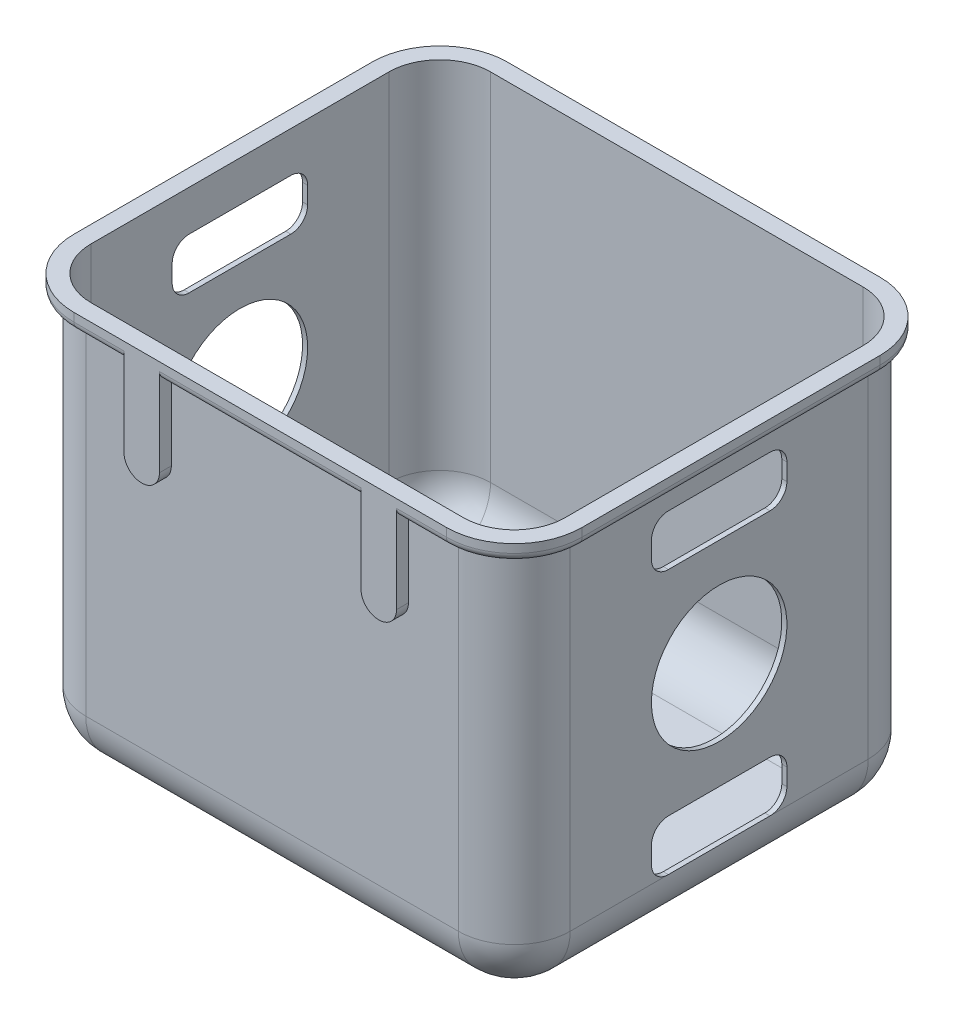
SolidWorks part; units mm, degrees
ref_plane "Front Plane" through (0, 0, 0) normal (0, 0, 1) x (1, 0, 0)
ref_plane "Top Plane" through (0, 0, 0) normal (0, 1, 0) x (1, 0, 0)
ref_plane "Right Plane" through (0, 0, 0) normal (1, 0, 0) x (0, 0, -1)
sketch "Sketch1" plane through (0, 0, 0) normal (0, 1, 0) x (1, 0, 0)
  line L1 (-145.5235, 110.6147) -> (140.4765, 110.6147)
  line L2 (-145.5235, 110.6147) -> (-145.5235, -131.3853)
  line L3 (-145.5235, -131.3853) -> (140.4765, -131.3853)
  line L4 (140.4765, 110.6147) -> (140.4765, -131.3853)
  dimension "D1" = 286
  dimension "D2" = 242
extrude "Boss-Extrude1" add sketch "Sketch1" along normal blind 243
fillet "Fillet1" radius 33 8 edges at (-2.5235, 0, 131.3853) (140.4765, 0, 10.3853) (-2.5235, 0, -110.6147) (-145.5235, 0, 10.3853) (-145.5235, 121.5, -110.6147) (-145.5235, 121.5, 131.3853) (140.4765, 121.5, -110.6147) (140.4765, 121.5, 131.3853)
shell "Shell1" thickness 3 removed face at (-2.5235, 243, 10.3853)
sketch "Sketch3" plane through (-145.5235, 0, 0) normal (-1, 0, 0) x (0, 0, 1)
  line L0 (-29.6147, 204) -> (50.3853, 204) construction
  line L5 (98.3853, 0) -> (-77.6147, 0) construction
  line L6 (-77.6147, 33) -> (98.3853, 33) construction
  line L7 (40.3853, 219) -> (-19.6147, 219)
  line L8 (50.3853, 209) -> (50.3853, 199)
  line L9 (40.3853, 189) -> (-19.6147, 189)
  line L10 (-29.6147, 209) -> (-29.6147, 199)
  line L11 (-110.6147, 33) -> (-110.6147, 243) construction
  line L12 (-19.6147, 63) -> (40.3853, 63)
  line L13 (-29.6147, 53) -> (-29.6147, 43)
  line L14 (-19.6147, 33) -> (40.3853, 33)
  line L15 (50.3853, 53) -> (50.3853, 43)
  arc A0 (40.3853, 33) -> (50.3853, 43) centre (40.3853, 43) ccw
  arc A1 (-29.6147, 43) -> (-19.6147, 33) centre (-19.6147, 43) ccw
  arc A2 (40.3853, 63) -> (50.3853, 53) centre (40.3853, 53) cw
  arc A3 (-19.6147, 63) -> (-29.6147, 53) centre (-19.6147, 53) ccw
  arc A4 (40.3853, 219) -> (50.3853, 209) centre (40.3853, 209) cw
  arc A5 (50.3853, 199) -> (40.3853, 189) centre (40.3853, 199) cw
  arc A6 (-19.6147, 189) -> (-29.6147, 199) centre (-19.6147, 199) cw
  arc A7 (-29.6147, 209) -> (-19.6147, 219) centre (-19.6147, 209) cw
  circle A12 centre (10.3853, 126) radius 40
  point P4 (10.3853, 204)
  point P28 (50.3853, 219)
  point P31 (50.3853, 189)
  point P38 (50.3853, 166)
  point P41 (50.3853, 86)
  point P46 (-29.6147, 166)
  dimension "D7" = 10
  dimension "D9" = 80
  dimension "D2" = 80
  dimension "D3" = 80
  dimension "D4" = 121
  dimension "D5" = 30
  dimension "D6" = 63
  dimension "D10" = 126
extrude "Cut-Extrude1" cut sketch "Sketch3" against normal through all
sketch "Sketch6" plane through (0, 243, 0) normal (0, 1, 0) x (1, 0, 0)
  line L0 (140.4765, -98.3853) -> (140.4765, 77.6147) construction
  line L1 (-112.5235, 117.6147) -> (107.4765, 117.6147)
  line L2 (-152.5235, 77.6147) -> (-152.5235, -98.3853)
  line L3 (-112.5235, -138.3853) -> (107.4765, -138.3853)
  line L4 (147.4765, 77.6147) -> (147.4765, -98.3853)
  line L5 (-112.5235, 110.6147) -> (107.4765, 110.6147)
  line L6 (-145.5235, 77.6147) -> (-145.5235, -98.3853)
  line L7 (-112.5235, -131.3853) -> (107.4765, -131.3853)
  line L8 (140.4765, 77.6147) -> (140.4765, -98.3853)
  line L9 (107.4765, 110.6147) -> (-112.5235, 110.6147) construction
  line L10 (-145.5235, 77.6147) -> (-145.5235, -98.3853) construction
  line L12 (-112.5235, -131.3853) -> (107.4765, -131.3853) construction
  arc A0 (-112.5235, -131.3853) -> (-145.5235, -98.3853) centre (-112.5235, -98.3853) cw
  arc A1 (107.4765, 110.6147) -> (140.4765, 77.6147) centre (107.4765, 77.6147) cw
  arc A2 (-145.5235, 77.6147) -> (-112.5235, 110.6147) centre (-112.5235, 77.6147) cw
  arc A3 (107.4765, -131.3853) -> (140.4765, -98.3853) centre (107.4765, -98.3853) ccw
  arc A4 (-112.5235, -138.3853) -> (-152.5235, -98.3853) centre (-112.5235, -98.3853) cw
  arc A5 (147.4765, 77.6147) -> (107.4765, 117.6147) centre (107.4765, 77.6147) ccw
  arc A6 (147.4765, -98.3853) -> (107.4765, -138.3853) centre (107.4765, -98.3853) cw
  arc A7 (-152.5235, 77.6147) -> (-112.5235, 117.6147) centre (-112.5235, 77.6147) cw
  point P20 (-145.5235, -131.3853)
  point P23 (140.4765, 110.6147)
  point P26 (-145.5235, 110.6147)
  dimension "D1" = 33
  dimension "D6" = 40
  dimension "D2" = 7
  dimension "D3" = 7
  dimension "D4" = 7
  dimension "D5" = 7
  dimension "D7" = 0
extrude "Boss-Extrude2" add sketch "Sketch6" against normal blind 10
fillet "Fillet2" radius 5 8 edges at (-140.8078, 233, 126.6696) (-152.5235, 233, 10.3853) (-140.8078, 233, -105.899) (-2.5235, 233, -117.6147) (135.7607, 233, -105.899) (147.4765, 233, 10.3853) (135.7607, 233, 126.6696) (-2.5235, 233, 138.3853)
sketch "Sketch7" plane through (0, 0, -117.6147) normal (0, 0, -1) x (-1, 0, 0)
  line L0 (-107.4765, 243) -> (112.5235, 243) construction
  line L1 (-87.4765, 243) -> (-47.4765, 243)
  line L2 (-87.4765, 243) -> (-87.4765, 225)
  line L3 (-87.4765, 225) -> (-47.4765, 225)
  line L4 (-47.4765, 243) -> (-47.4765, 225)
  line L5 (-47.4765, 225) -> (52.5235, 225) construction
  line L6 (52.5235, 243) -> (92.5235, 243)
  line L7 (52.5235, 243) -> (52.5235, 225)
  line L8 (52.5235, 225) -> (92.5235, 225)
  line L9 (92.5235, 243) -> (92.5235, 225)
  line L10 (2.5235, 243) -> (2.5235, 225) construction
  dimension "D1" = 18
  dimension "D2" = 40
  dimension "D3" = 100
extrude "Boss-Extrude3" add sketch "Sketch7" against normal up to next
sketch "Sketch9" plane through (0, 0, 138.3853) normal (0, 0, 1) x (1, 0, 0)
  line L0 (-112.5235, 243) -> (107.4765, 243) construction
  line L1 (-83.0235, 243) -> (-62.0235, 243)
  line L2 (-83.0235, 243) -> (-83.0235, 186.25)
  line L3 (-83.0235, 186.25) -> (-62.0235, 186.25)
  line L4 (-62.0235, 243) -> (-62.0235, 186.25)
  line L5 (-62.0235, 186.25) -> (56.9765, 186.25) construction
  line L6 (56.9765, 243) -> (77.9765, 243)
  line L7 (56.9765, 243) -> (56.9765, 186.25)
  line L8 (56.9765, 186.25) -> (77.9765, 186.25)
  line L9 (77.9765, 243) -> (77.9765, 186.25)
  line L10 (-2.5235, 186.25) -> (-2.5235, 243) construction
  circle A0 centre (-72.5235, 186.25) radius 10.5
  circle A1 centre (67.4765, 186.25) radius 10.5
  line M12 (-112.5235, 238) -> (107.4765, 238)
  line M14 (107.4765, 243) -> (-112.5235, 243)
  dimension "D2" = 21
  dimension "D1" = 140
  dimension "D3" = 56.75
extrude "Boss-Extrude5" add sketch "Sketch9" against normal up to next contours A0 L4 L2 M12 | L3 A0 | L8 A1 | L8 A1 | A1 L9 L7 M12 | L4 L2 M14 M12 | L9 L7 M14 M12 | L3 A0 region at (-72.5235, 240.5, 138.3853) region at (-72.5235, 216.1852, 138.3853) region at (67.4765, 240.5, 138.3853) region at (-72.5235, 190.7063, 138.3853) region at (-72.5235, 181.7937, 138.3853) region at (67.4765, 216.1852, 138.3853) region at (67.4765, 190.7063, 138.3853) region at (67.4765, 181.7937, 138.3853)
sketch "Sketch8" plane through (0, 0, 0) normal (0, -1, 0) x (1, 0, 0)
  line L0 (107.4765, -77.6147) -> (107.4765, 98.3853) construction
  line L1 (107.4765, 98.3853) -> (-112.5235, 98.3853) construction
  line L2 (-112.5235, -77.6147) -> (107.4765, -77.6147) construction
  line L3 (-112.5235, 98.3853) -> (-112.5235, -77.6147) construction
  circle A0 centre (92.4765, 83.3853) radius 15
  circle A1 centre (92.4765, -62.6147) radius 15
  circle A2 centre (-97.5235, 83.3853) radius 15
  circle A3 centre (-97.5235, -62.6147) radius 15
  dimension "D1" = 30
extrude "Boss-Extrude4" add sketch "Sketch8" along normal blind 5
fillet "Fillet3" radius 5 4 edges at (-97.5235, -5, 68.3853) (92.4765, -5, 68.3853) (92.4765, -5, -77.6147) (-97.5235, -5, -77.6147)
equation "\"D3@Sketch6\"=\"D2@Sketch6\""
equation "\"D4@Sketch6\"=\"D2@Sketch6\""
equation "\"D5@Sketch6\"=\"D3@Sketch6\""
